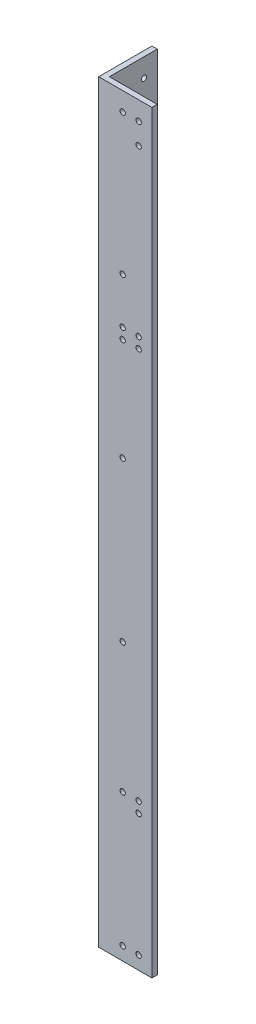
SolidWorks part; units mm, degrees
ref_plane "Front Plane" through (0, 0, 0) normal (0, 0, 1) x (1, 0, 0)
ref_plane "Top Plane" through (0, 0, 0) normal (0, 1, 0) x (1, 0, 0)
ref_plane "Right Plane" through (0, 0, 0) normal (1, 0, 0) x (0, 0, -1)
sketch "Sketch2" plane through (0, 0, 0) normal (0, 1, 0) x (1, 0, 0)
  line L0 (0, 31.75) -> (3.175, 31.75)
  line L1 (3.175, 31.75) -> (3.175, 3.175)
  line L2 (3.175, 3.175) -> (31.75, 3.175)
  line L3 (31.75, 3.175) -> (31.75, 0)
  line L4 (31.75, 0) -> (0, 0)
  line L5 (0, 0) -> (0, 31.75)
  point P9 (1.5875, 31.75)
  point P10 (31.75, 1.5875)
  dimension "D4" = 3.175
  dimension "D1" = 31.75
  dimension "D2" = 31.75
  dimension "D3" = 3.175
extrude "Boss-Extrude1" add sketch "Sketch2" along normal blind 450
sketch "BackSideHoles-Sketch3" plane through (0, 0, 0) normal (0, 0, 1) x (1, 0, 0)
  line L0 (0, 0) -> (31.75, 0) construction
  line L1 (0, 450) -> (0, 0) construction
  circle A1 centre (23.8125, 81.1125) radius 1.5875
  circle A2 centre (14.2875, 87.4625) radius 1.5875
  circle A3 centre (23.8125, 87.4625) radius 1.5875
  circle A4 centre (14.2875, 438.8875) radius 1.5875
  circle A6 centre (23.8125, 438.8875) radius 1.5875
  circle A7 centre (23.8125, 426.1875) radius 1.5875
  circle A10 centre (14.2875, 327.6026) radius 1.5875
  circle A11 centre (23.8125, 327.6026) radius 1.5875
  circle A12 centre (14.2875, 321.2526) radius 1.5875
  circle A13 centre (23.8125, 321.2526) radius 1.5875
  circle A14 centre (14.2875, 165) radius 1.5875
  circle A15 centre (14.2875, 260) radius 1.5875
  circle A16 centre (14.2875, 355) radius 1.5875
  circle A17 centre (14.2875, 7.9375) radius 1.5875
  circle A18 centre (23.8125, 7.9375) radius 1.5875
  dimension "D4" = 3.175
  dimension "D8" = 11.1125
  dimension "D7" = 6.35
  dimension "D10" = 327.6026
  dimension "D11" = 165
  dimension "D12" = 95
  dimension "D13" = 95
  dimension "D6" = 7.9375
  dimension "D5" = 6.35
  dimension "D14" = 81.1125
  dimension "D3" = 9.525
  dimension "D2" = 14.2875
  dimension "D9" = 12.7
sketch "RightSideHoles-Sketch4" plane through (0, 0, 0) normal (-1, 0, 0) x (0, 0, 1)
  line L0 (-31.75, 450) -> (0, 450) construction
  line L1 (0, 450) -> (0, 0) construction
  line L3 (-31.75, 0) -> (0, 0) construction
  circle A0 centre (-23.8125, 81.1125) radius 1.5875
  circle A2 centre (-23.8125, 87.4625) radius 1.5875
  circle A4 centre (-23.8125, 438.8875) radius 1.5875
  circle A5 centre (-14.2875, 426.1875) radius 1.5875
  circle A6 centre (-23.8125, 426.1875) radius 1.5875
  circle A10 centre (-23.8125, 327.6026) radius 1.5875
  circle A11 centre (-14.2875, 327.6026) radius 1.5875
  circle A12 centre (-23.8125, 292.6776) radius 1.5875
  circle A13 centre (-14.2875, 292.6776) radius 1.5875
  circle A14 centre (-23.8125, 7.9375) radius 1.5875
  circle A15 centre (-14.2875, 7.9375) radius 1.5875
  circle A16 centre (-14.2875, 165) radius 1.5875
  circle A17 centre (-14.2875, 260) radius 1.5875
  circle A18 centre (-14.2875, 355) radius 1.5875
  circle A19 centre (-14.2875, 81.1125) radius 1.5875
  dimension "D4" = 3.175
  dimension "D10" = 327.6026
  dimension "D13" = 95
  dimension "D5" = 6.35
  dimension "D2" = 14.2875
  dimension "D6" = 11.1125
  dimension "D8" = 7.9375
  dimension "D9" = 34.925
  dimension "D7" = 12.7
  dimension "D12" = 165
  dimension "D14" = 95
  dimension "D3" = 81.1125
  dimension "D11" = 9.525
extrude "BackSideHoles-Cut-Extrude1" cut sketch "BackSideHoles-Sketch3" against normal blind 3.175
extrude "RightSideHoles-Cut-Extrude2" cut sketch "RightSideHoles-Sketch4" against normal blind 3.175
equation "\"RailThickness\"= .125in'Spec"
equation "\"VSWidth\"= 1.25in'Spec"
equation "\"VSHeight\"= 1.25in'Spec"
equation "\"VSLength\"= 450mm"
equation "\"HoleOffsetFromEdge\"= \"RailThickness\" * 2.5"
equation "\"HoleOffsetFromSide\"= \"RailThickness\" * 3.5"
equation "\"LegHeight\"= 70mm'Space needed for PSU/Stepper/Electronics"
equation "\"VSBottomSideRailHoleY1FromBottomOfLowerRail\"= \"V1 BottomOfLowerRail\" + \"HoleOffsetFromSide\"'Equals 70.1125"
equation "\"VSSideRailHoleX1FromSide\"= \"HoleOffsetFromSide\" + \"RailThickness\""
equation "\"FasteningHoleDiameter\"= .125in"
equation "\"VSBottomSideRailHoleY2FromY1\"=  \"LowerRailHeight\" - \"HoleOffsetFromSide\" - \"HoleOffsetFromEdge\"'Equals 6.35"
equation "\"VSTopSideRailHoleY1FromEdge\"= \"HoleOffsetFromEdge\" + \"RailThickness\""
equation "\"D4@BackSideHoles-Sketch3\" = \"FasteningHoleDiameter\""
equation "\"D1@Boss-Extrude1\"=\"VSLength\""
equation "\"D4@RightSideHoles-Sketch4\"=\"FasteningHoleDiameter\""
equation "\"D8@BackSideHoles-Sketch3\" = \"VSTopSideRailHoleY1FromEdge\""
equation "\"D6@RightSideHoles-Sketch4\"=\"VSTopSideRailHoleY1FromEdge\""
equation "\"VSMidSideRailHoleY1FromV8TopOfMidSideRail\"= \"V8 ToTopOfMidSideRail\" - \"HoleOffsetFromEdge\"'Equals 308.2875"
equation "\"LowerRailHeight\"= 1.00in"
equation "\"D2@Sketch2\"=\"VSWidth\""
equation "\"D1@Sketch2\"=\"VSHeight\""
equation "\"MidBackRailHeight\"= 1.00in"
equation "\"VSMidBackRailHoleY1FromV7TopOfMidBackRail\"= \"V7 ToTopOfMidBackRail\" - \"HoleOffsetFromSide\"'Equals 308.2875"
equation "\"TopRailHeight\"= 1.25in"
equation "\"MidLeftOrRightSideRailHeight\"= 2.0in"
equation "\"D8@RightSideHoles-Sketch4\"=\"HoleOffsetFromEdge\""
equation "\"VSMidBackRailHoleY2FromY1\"= \"MidBackRailHeight\" - \"HoleOffsetFromSide\" - \"HoleOffsetFromEdge\"'Equals 6.35"
equation "\"VSMidSideRailHoleY2FromY1\"= \"MidLeftOrRightSideRailHeight\" - \"HoleOffsetFromEdge\" * 2'Equals 34.926"
equation "\"D7@BackSideHoles-Sketch3\"=\"VSMidBackRailHoleY2FromY1\""
equation "\"D9@RightSideHoles-Sketch4\"=\"VSMidSideRailHoleY2FromY1\""
equation "\"VSTopSideRailHoleY2FromY1\"= \"TopRailHeight\" - \"VSTopSideRailHoleY1FromEdge\" - \"HoleOffsetFromEdge\"'Equals 12.7"
equation "\"VSSideRailHoleX2FromX1\"= \"VSWidth\" - \"VSSideRailHoleX1FromSide\" - \"HoleOffsetFromEdge\""
equation "\"D7@RightSideHoles-Sketch4\"=\"VSTopSideRailHoleY2FromY1\""
equation "\"V1 BottomOfLowerRail\"= \"LegHeight\""
equation "\"StepperShaftLength\"= 24mm'Pulley will be attached to the end"
equation "\"ZAxisLeadScrewLength\"= 200mm"
equation "\"HotEndToTopOfXAxisGB\"= 63.315144mm'Measured from the100.Should be 63.315144"
equation "\"TopOfGBToBottomOfLinearRail\"= \"LinearGBWidth\" / 2 + \"LinearRailWidth\" / 2"
equation "\"LinearGBWidth\"= 27mm'Spec"
equation "\"V5 ToBottomOfXAxisLinearRail\"= \"V4 ToTopOfBuildPlate/HotEndTip\" + \"HotEndToTopOfXAxisGB\" - \"TopOfGBToBottomOfLinearRail\""
equation "\"LinearRailWidth\"= 12mm'Spec"
equation "\"V6 ToBottomOfGantryPulley\"= \"V5 ToBottomOfXAxisLinearRail\" - \"DistanceFromGABTopToLowerPulley\""
equation "\"GABUpperHeight\"= 6mm"
equation "\"GABMidWallHeight\"= 28mm'Must equal 28 or changes alignment"
equation "\"20TGT2PulleyWidth\"= 8.7mm'The STL of the Pulley in the diagram is a bit larger"
equation "\"GABMidShortRiserHeight\"= \"GABMidWallHeight\" / 2 - \"20TGT2PulleyWidth\"'Equals 5.3"
equation "\"GABRiserBossOffset\"= 0.8mm'Aligns Pulleys"
equation "\"DistanceFromGABTopToLowerPulley\"= \"GABUpperHeight\" + \"GABMidWallHeight\" - \"GABMidShortRiserHeight\" + \"GABRiserBossOffset\" / 2"
equation "\"V7 ToTopOfMidBackRail\"= \"V6 ToBottomOfGantryPulley\" + \"StepperShaftLength\""
equation "\"D10@BackSideHoles-Sketch3\" = \"VSMidBackRailHoleY1FromV7TopOfMidBackRail\""
equation "\"D10@RightSideHoles-Sketch4\"=\"VSMidSideRailHoleY1FromV8TopOfMidSideRail\""
equation "\"BedToBuildPlateStandoffLength\"= 15mm"
equation "\"BuildPlateHeight\"= 8mm'Spec"
equation "\"V4 ToTopOfBuildPlate/HotEndTip\"= \"V2 ToBedAtTopOfZAxis\" + \"BedToBuildPlateStandoffLength\" + \"BuildPlateHeight\""
equation "\"V2 ToBedAtTopOfZAxis\"= \"V1 BottomOfLowerRail\" - \"LowerEnclosureThickness\" + \"StepperShaftLength\" + \"ZAxisLeadScrewLength\" - \"LM8UUHeight\" / 2"
equation "\"LM8UUHeight\"= 24mm'Spec"
equation "\"V8 ToTopOfMidSideRail\"= \"V7 ToTopOfMidBackRail\" - \"RailThickness\""
equation "\"VSEnclosureOffsets\"= ( \"VSLength\" - \"LegHeight\" ) / 4"
equation "\"D11@BackSideHoles-Sketch3\"=\"LegHeight\" + \"VSEnclosureOffsets\""
equation "\"D12@BackSideHoles-Sketch3\"=\"VSEnclosureOffsets\""
equation "\"D13@BackSideHoles-Sketch3\"=\"VSEnclosureOffsets\""
equation "\"D12@RightSideHoles-Sketch4\"=\"LegHeight\" + \"VSEnclosureOffsets\""
equation "\"D13@RightSideHoles-Sketch4\"=\"VSEnclosureOffsets\""
equation "\"D14@RightSideHoles-Sketch4\"=\"VSEnclosureOffsets\""
equation "\"D6@BackSideHoles-Sketch3\"=\"HoleOffsetFromEdge\""
equation "\"D5@BackSideHoles-Sketch3\"=\"VSBottomSideRailHoleY2FromY1\""
equation "\"D14@BackSideHoles-Sketch3\"=\"VSBottomSideRailHoleY1FromBottomOfLowerRail\""
equation "\"D2@BackSideHoles-Sketch3\"=\"VSSideRailHoleX1FromSide\""
equation "\"D9@BackSideHoles-Sketch3\"=\"VSTopSideRailHoleY2FromY1\""
equation "\"D3@RightSideHoles-Sketch4\"=\"VSBottomSideRailHoleY1FromBottomOfLowerRail\""
equation "\"D5@RightSideHoles-Sketch4\"=\"VSBottomSideRailHoleY2FromY1\""
equation "\"D2@RightSideHoles-Sketch4\"=\"VSSideRailHoleX1FromSide\""
equation "\"D11@RightSideHoles-Sketch4\"=\"VSSideRailHoleX2FromX1\""
equation "\"LowerEnclosureThickness\"= 5mm"
